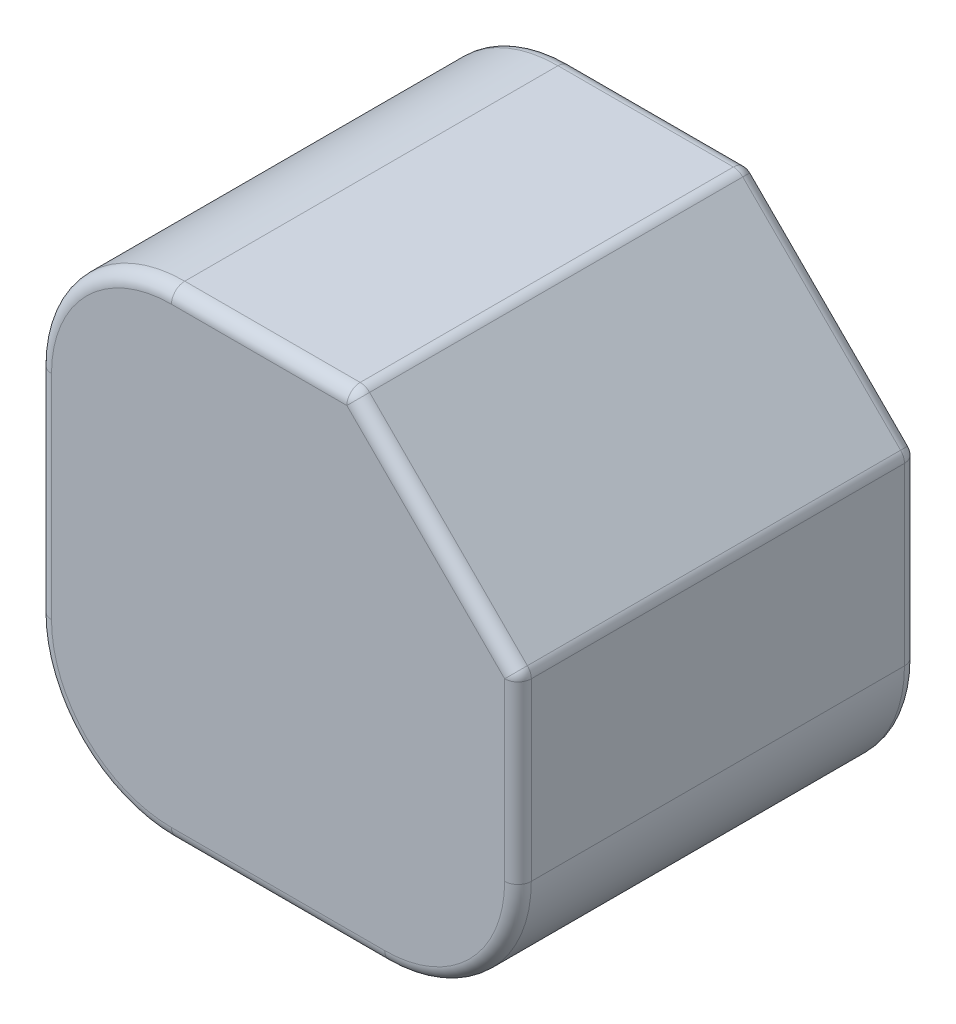
SolidWorks part; units mm, degrees
material "Stainless Steel (ferritic)"
ref_plane "Front Plane" through (0, 0, 0) normal (0, 0, 1) x (1, 0, 0)
ref_plane "Top Plane" through (0, 0, 0) normal (0, 1, 0) x (1, 0, 0)
ref_plane "Right Plane" through (0, 0, 0) normal (1, 0, 0) x (0, 0, -1)
sketch "Sketch1" plane through (0, 0, 0) normal (0, 0, 1) x (1, 0, 0)
  line L1 (0, 0) -> (-36, 0)
  line L2 (0, 0) -> (0, -36)
  line L3 (0, -36) -> (-36, -36)
  line L4 (-36, 0) -> (-36, -36)
  dimension "D1" = 36
extrude "Boss-Extrude1" add sketch "Sketch1" along normal mid plane 30
sketch "Sketch2" plane through (0, -36, 0) normal (0, -1, 0) x (1, 0, 0)
  line L0 (-36, 0) -> (0, 0) construction
  line L1 (-36, 15) -> (-36, -15) construction
  line L2 (0, 15) -> (0, -15) construction
  circle A0 centre (-19.294, 0) radius 10
  dimension "D2" = 20
  dimension "D1" = 16.706
extrude "Cut-Extrude1" cut sketch "Sketch2" against normal blind 4
sketch "Sketch4" plane through (-36, 0, 0) normal (-1, 0, 0) x (0, 0, 1)
  line L2 (0, 0) -> (0, -19.294) construction
  line L3 (15, 0) -> (-15, 0) construction
  line L4 (15, -36) -> (-15, -36) construction
  circle A0 centre (0, -19.294) radius 10
  dimension "D2" = 20
  dimension "D1" = 16.706
extrude "Cut-Extrude2" cut sketch "Sketch4" against normal blind 4
hole_wizard "M8x1.0 Tapped Hole1" positions "Sketch6" profile "Sketch5" tap size "M8x1.0" standard "Ansi Metric"
sketch "Sketch6" plane through (-32, 0, 0) normal (-1, 0, 0) x (0, 0, 1)
  circle A0 centre (0, -19.294) radius 10 construction
  point P0 (0, -19.294)
sketch "Sketch5" plane through (-32, -19.294, 0) normal (0, 1, 0) x (0, 0, 1)
  line L0 (0, 0) -> (0, 17.103)
  line L1 (0, 17.103) -> (3.5, 15)
  line L2 (3.5, 15) -> (3.5, 0)
  line L5 (3.5, 0) -> (0, 0)
  line L10 (0, 17.103) -> (-3.5, 15) construction
  line L11 (0, -6.35) -> (0, 107.95) construction
  dimension "Tap Drill Dia." = 7
  dimension "Tap Drill Depth" = 15
  dimension "Drill Angle" = 118
cosmetic thread "Hole Thread1" parameters "D1"=12, "D2"=8
hole_wizard "M8x1.0 Tapped Hole2" positions "Sketch8" profile "Sketch7" tap size "M8x1.0" standard "Ansi Metric"
sketch "Sketch8" plane through (0, -32, 0) normal (0, -1, 0) x (1, 0, 0)
  circle A0 centre (-19.294, 0) radius 10 construction
  point P0 (-19.294, 0)
sketch "Sketch7" plane through (-19.294, -32, 0) normal (1, 0, 0) x (0, 0, -1)
  line L0 (0, 0) -> (0, 17.103)
  line L1 (0, 17.103) -> (3.5, 15)
  line L2 (3.5, 15) -> (3.5, 0)
  line L5 (3.5, 0) -> (0, 0)
  line L10 (0, 17.103) -> (-3.5, 15) construction
  line L11 (0, -6.35) -> (0, 107.95) construction
  dimension "Tap Drill Dia." = 7
  dimension "Tap Drill Depth" = 15
  dimension "Drill Angle" = 118
cosmetic thread "Hole Thread2" parameters "D1"=12, "D2"=8
fillet "Fillet1" radius 10 3 edges at (-36, -36, 0) (-36, 0, 0) (0, -36, 0)
hole_wizard "M4x0.7 Tapped Hole1" positions "Sketch11" profile "Sketch10" tap size "M4x0.7" standard "Ansi Metric"
sketch "Sketch11" plane through (0, 0, -15) normal (0, 0, -1) x (-1, 0, 0)
  line L0 (19.294, -36) -> (19.294, -19.294) construction
  line L1 (26, -36) -> (10, -36) construction
  line L2 (19.294, -19.294) -> (36, -19.294) construction
  line L3 (36, -10) -> (36, -26) construction
  line L7 (0, 0) -> (33.0711, -33.0711) construction
  line L9 (19.294, -19.294) -> (4.8051, -23.1763) construction
  line L12 (19.294, -19.294) -> (23.1763, -4.8051) construction
  circle A0 centre (19.294, -19.294) radius 15 construction
  arc A1 (26, -36) -> (36, -26) centre (26, -26) ccw construction
  point P0 (29.9006, -29.9006)
  point P42 (4.8051, -23.1763)
  point P44 (23.1763, -4.8051)
  dimension "D2" = 30
  dimension "D1" = 16.706
  dimension "D3" = 120
  dimension "D4" = 120
sketch "Sketch10" plane through (-29.9006, -29.9006, -15) normal (1, 0, 0) x (0, 1, 0)
  line L0 (0, 0) -> (0, 11.0914)
  line L1 (0, 11.0914) -> (1.65, 10.1)
  line L2 (1.65, 10.1) -> (1.65, 0)
  line L5 (1.65, 0) -> (0, 0)
  line L10 (0, 11.0914) -> (-1.65, 10.1) construction
  line L11 (0, -6.35) -> (0, 107.95) construction
  dimension "Tap Drill Dia." = 3.3
  dimension "Tap Drill Depth" = 10.1
  dimension "Drill Angle" = 118
cosmetic thread "Hole Thread3" parameters "D1"=8, "D2"=4
cosmetic thread "Hole Thread4" parameters "D1"=8, "D2"=4
cosmetic thread "Hole Thread5" parameters "D1"=8, "D2"=4
sketch "Sketch12" plane through (0, 0, -15) normal (0, 0, -1) x (-1, 0, 0)
  line L0 (0, -12.425) -> (12.425, 0)
  line L1 (0, -26) -> (0, 0) construction
  line L2 (0, 0) -> (26, 0) construction
  line L3 (0, -12.425) -> (0, 0)
  line L4 (0, 0) -> (12.425, 0)
  line L5 (3.9455, -13.4293) -> (12.7744, -4.6004) construction
  circle A0 centre (19.294, -19.294) radius 15 construction
  dimension "D1" = 7
extrude "Cut-Extrude3" cut sketch "Sketch12" against normal through all
sketch "Sketch13" plane through (0, 0, 15) normal (0, 0, 1) x (1, 0, 0)
  line L0 (-19.294, -36) -> (-19.294, -19.294) construction
  line L1 (-26, -36) -> (-10, -36) construction
  line L2 (-19.294, -19.294) -> (-36, -19.294) construction
  line L3 (-36, -10) -> (-36, -26) construction
  dimension "D1" = 16.706
ref_axis "Axis1" through (-19.294, -19.294, 15) along (0, 0, -1)
fillet "Fillet2" radius 1 18 edges at (0, -19.2125, 15) (-2.9289, -33.0711, 15) (-18, -36, 15) (-33.0711, -33.0711, 15) (-36, -18, 15) (-33.0711, -2.9289, 15) (-33.0711, -2.9289, -15) (-36, -18, -15) (-33.0711, -33.0711, -15) (0, -19.2125, -15) (-2.9289, -33.0711, -15) (-19.2125, 0, -15) (-19.2125, 0, 15) (0, -12.425, 0) (-6.2125, -6.2125, 15) (-12.425, 0, 0) (-6.2125, -6.2125, -15) (-18, -36, -15)
